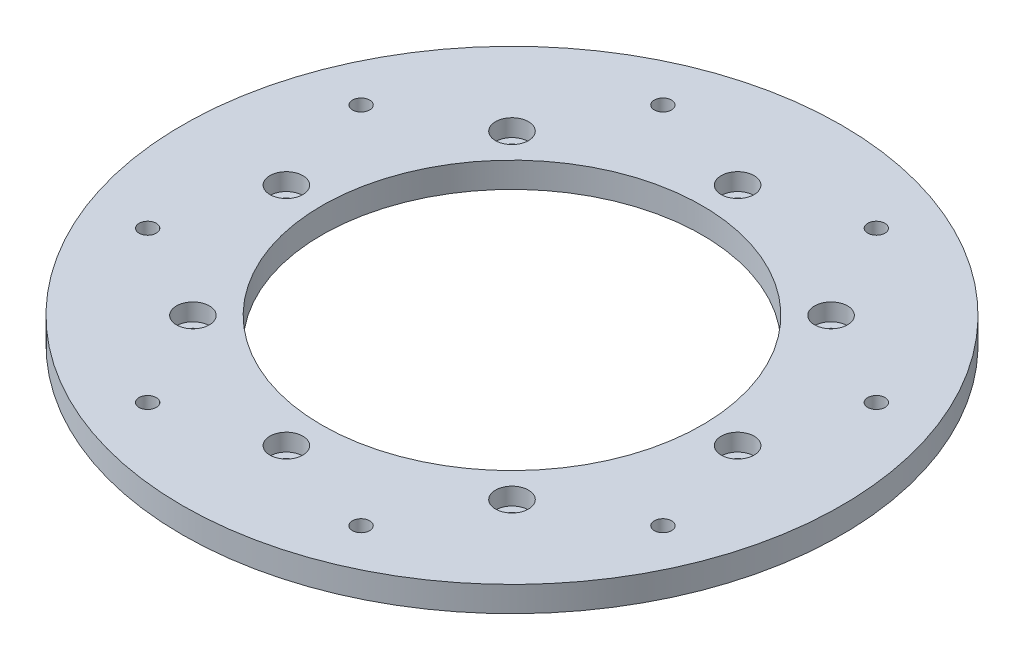
SolidWorks part; units mm, degrees
material "6061-T6 (SS)"
ref_plane "Front Plane" through (0, 0, 0) normal (0, 0, 1) x (1, 0, 0)
ref_plane "Top Plane" through (0, 0, 0) normal (0, 1, 0) x (1, 0, 0)
ref_plane "Right Plane" through (0, 0, 0) normal (1, 0, 0) x (0, 0, -1)
sketch "Sketch1" plane through (0, 0, 0) normal (0, 1, 0) x (1, 0, 0)
  circle A0 centre (0, 0) radius 37.5
  circle A1 centre (0, 0) radius 65
  dimension "D1" = 75
  dimension "D2" = 130
extrude "Boss-Extrude1" add sketch "Sketch1" along normal blind 5
sketch "Sketch4" plane through (0, 5, 0) normal (0, 1, 0) x (1, 0, 0)
  circle A0 centre (0, 0) radius 44.5 construction
  point P4 (0, 44.5)
  point P13 (31.4663, 31.4663)
  point P14 (44.5, 0)
  point P15 (31.4663, -31.4663)
  point P16 (0, -44.5)
  point P17 (-31.4663, -31.4663)
  point P18 (-44.5, 0)
  point P19 (-31.4663, 31.4663)
  dimension "D1" = 89
  dimension "D2" = 8
hole_wizard "CBORE for M3 Hex Socket Head Cap Screw1" positions "Sketch4" profile "Sketch3" counterbore size "M3" standard "DIN" end condition through all
sketch "Sketch3" plane through (-31.4663, 5, -31.4663) normal (1, 0, 0) x (0, 0, 1)
  line L0 (0, 0) -> (0, 5)
  line L1 (0, 5) -> (1.7, 5)
  line L3 (1.7, 5) -> (1.7, 3.4)
  line L4 (1.7, 3.4) -> (3.25, 3.4)
  line L5 (3.25, 3.4) -> (3.25, 0)
  line L7 (3.25, 0) -> (0, 0)
  line L11 (0, -6.35) -> (0, 107.95) construction
  dimension "Thru Hole Dia." = 3.4
  dimension "Thru Hole Depth" = 5
  dimension "C'Bore Dia." = 6.5
  dimension "C'Bore Depth" = 3.4
sketch "Sketch7" plane through (0, 0, 0) normal (0, -1, 0) x (-1, 0, 0)
  line L0 (0, 0) -> (-61.0389, 25.2831) construction
  circle A0 centre (0, 0) radius 55
  point P9 (-50.8134, 21.0476)
  point P17 (-21.0476, 50.8134)
  point P18 (21.0476, 50.8134)
  point P19 (50.8134, 21.0476)
  point P20 (50.8134, -21.0476)
  point P21 (21.0476, -50.8134)
  point P22 (-21.0476, -50.8134)
  point P23 (-50.8134, -21.0476)
  dimension "D1" = 22.5
  dimension "D2" = 110
  dimension "D3" = 8
hole_wizard "M3 Clearance Hole1" positions "Sketch7" profile "Sketch6" hole size "M3" standard "DIN" end condition through all
sketch "Sketch6" plane through (50.8134, 0, 21.0476) normal (1, 0, 0) x (0, 0, -1)
  line L0 (0, 0) -> (0, 5)
  line L1 (0, 5) -> (1.7, 5)
  line L2 (1.7, 5) -> (1.7, 0)
  line L5 (1.7, 0) -> (0, 0)
  line L11 (0, -6.35) -> (0, 107.95) construction
  dimension "Thru Hole Dia." = 3.4
  dimension "Thru Hole Depth" = 5
